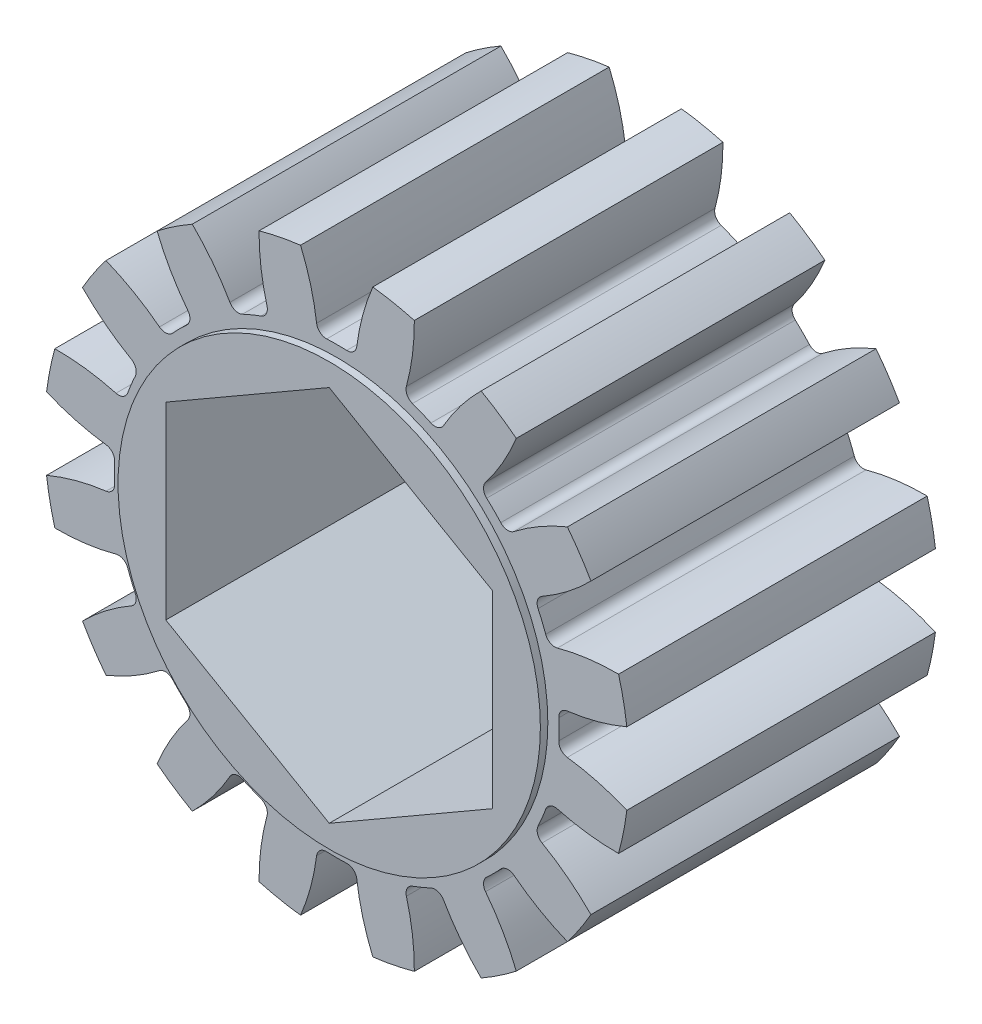
SolidWorks part; units mm, degrees
material "7075-T6 (SN)"
ref_plane "Alzado" through (0, 0, 0) normal (0, 0, 1) x (1, 0, 0)
ref_plane "Planta" through (0, 0, 0) normal (0, 1, 0) x (1, 0, 0)
ref_plane "Vista lateral" through (0, 0, 0) normal (1, 0, 0) x (0, 0, -1)
sketch "Croquis1" plane through (0, 0, 0) normal (0, 0, 1) x (1, 0, 0)
  circle A0 centre (0, 0) radius 10.16 construction
  circle A1 centre (0, 0) radius 11.43
  dimension "D" = 20.32
  dimension "OD" = 22.86
extrude "Saliente-Extruir1" add sketch "Croquis1" along normal mid plane 12.065
sketch "Croquis2" plane through (0, 0, 0) normal (0, 0, 1) x (1, 0, 0)
  line L0 (0, 0) -> (0, 11.43) construction
  line L1 (0, 0) -> (4.3741, 10.5599) construction
  line L2 (0, 0) -> (2.2299, 11.2104) construction
  line L3 (-0.7471, 8.6584) -> (0, 0) construction
  line L4 (-0.9959, 10.1111) -> (0.9959, 10.1111) construction
  line L5 (0.9959, 10.1111) -> (2.9493, 9.7225) construction
  line L6 (-1.3173, 11.3538) -> (0, 6.2604) construction
  circle A0 centre (0, 0) radius 11.43 construction
  arc A2 (0.7471, 8.6584) -> (-0.7471, 8.6584) centre (0, 0) ccw
  circle A5 centre (0, 0) radius 10.16 construction
  arc A6 (-1.4131, 11.3423) -> (-0.7471, 8.6584) centre (-9.5499, 7.8988) cw
  arc A7 (1.4131, 11.3423) -> (0.7471, 8.6584) centre (9.5499, 7.8988) ccw
  arc A8 (1.4131, 11.3423) -> (-1.4131, 11.3423) centre (0, 0) ccw
  dimension "D1" = 22.5
  dimension "D2" = 11.25
  dimension "B" = 1.4694
  dimension "Pressure Angle" = 14.5
extrude "Cortar-Extruir1" cut sketch "Croquis2" against normal through all both and the other way through all
fillet "Redondeo1" radius 0.381 2 edges at (0.7471, 8.6584, 0) (-0.7471, 8.6584, 0)
pattern_circular "MatrizC1" count 16 over 360 about axis through (0, 0, 6.0325) along (0, 0, -1) of "Cortar-Extruir1", "Redondeo1"
sketch "Croquis3" plane through (0, 0, 0) normal (0, 0, 1) x (1, 0, 0)
  circle A0 centre (0, 0) radius 8.255
  dimension "sp" = 16.51
extrude "Saliente-Extruir2" add sketch "Croquis3" along normal mid plane 12.6492
sketch "Croquis4" plane through (0, 0, 0) normal (0, 0, 1) x (1, 0, 0)
  line L1 (0, 7.3763) -> (-6.3881, 3.6882)
  line L2 (-6.3881, 3.6882) -> (-6.3881, -3.6882)
  line L3 (-6.3881, -3.6882) -> (0, -7.3763)
  line L4 (0, -7.3763) -> (6.3881, -3.6882)
  line L5 (6.3881, -3.6882) -> (6.3881, 3.6882)
  line L6 (6.3881, 3.6882) -> (0, 7.3763)
  circle A0 centre (0, 0) radius 6.3881 construction
  dimension "D1" = 12.7762
extrude "Cortar-Extruir2" cut sketch "Croquis4" against normal through all both and the other way through all
equation "\"Number of teeth\" = 16"
equation "\"Diametral Pitch\"= 20"
equation "\"Pressure Angle\"= 14.5"
equation "\"D@Croquis1\"=\"Number of teeth\"/\"Diametral Pitch\""
equation "\"OD@Croquis1\"=(\"Number of teeth\"+2) /\"Diametral Pitch\""
equation "\"D2@Croquis2\"=(360 / \"Number of teeth\")/ 2."
equation "\"D1@Croquis2\"=360 / \"Number of teeth\""
equation "\"B@Croquis2\"=1.157 / \"Diametral Pitch\""
equation "\"Pressure Angle@Croquis2\" = \"Pressure Angle\""
equation "\"D1@Redondeo1\"=(pi / \"Diametral Pitch\") * .0955"
equation "\"D1@MatrizC1\"=\"Number of teeth\""
equation "\"Tt@Saliente-Extruir1\"=if( \"Number of teeth\"=>30,0.375,0.475)"
equation "\"sp@Croquis3\"=if( \"Number of teeth\"=16,0.65,0.7)"
